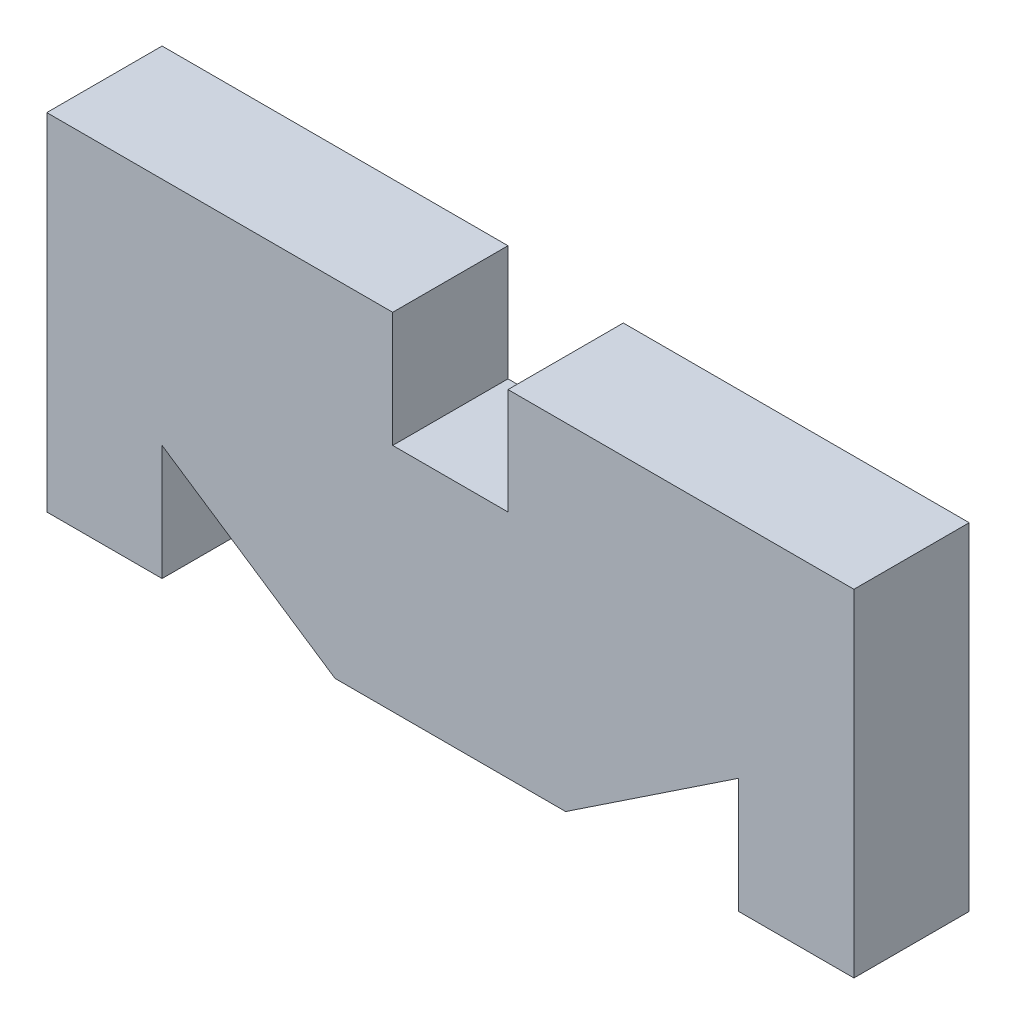
SolidWorks part; units mm, degrees
ref_plane "Front Plane" through (0, 0, 0) normal (0, 0, 1) x (1, 0, 0)
ref_plane "Top Plane" through (0, 0, 0) normal (0, 1, 0) x (1, 0, 0)
ref_plane "Right Plane" through (0, 0, 0) normal (1, 0, 0) x (0, 0, -1)
sketch "Sketch1" plane through (0, 0, 0) normal (0, 0, 1) x (1, 0, 0)
  line L0 (-21.9643, 0) -> (-21.9643, 30)
  line L1 (-21.9643, 30) -> (8.0357, 30)
  line L2 (8.0357, 30) -> (8.0357, 20)
  line L3 (8.0357, 20) -> (18.0357, 20)
  line L4 (18.0357, 20) -> (18.0357, 29.1964)
  line L5 (18.0357, 29.1964) -> (48.0357, 29.1964)
  line L6 (48.0357, 29.1964) -> (48.0357, 0)
  line L7 (48.0357, 0) -> (38.0357, 0)
  line L8 (38.0357, 0) -> (38.0357, 10)
  line L9 (38.0357, 10) -> (23.0357, 0)
  line L10 (23.0357, 0) -> (3.0357, 0)
  line L11 (3.0357, 0) -> (-11.9643, 10)
  line L12 (-11.9643, 10) -> (-11.9643, 0)
  line L13 (-11.9643, 0) -> (-21.9643, 0)
  dimension "D1" = 10
  dimension "D2" = 30
  dimension "D3" = 30
  dimension "D4" = 10
  dimension "D5" = 10
  dimension "D6" = 20
  dimension "D7" = 15
  dimension "D8" = 15
  dimension "D9" = 10
  dimension "D10" = 30
  dimension "D11" = 20
  dimension "D12" = 10
  dimension "D13" = 10
extrude "Boss-Extrude1" add sketch "Sketch1" along normal blind 10
